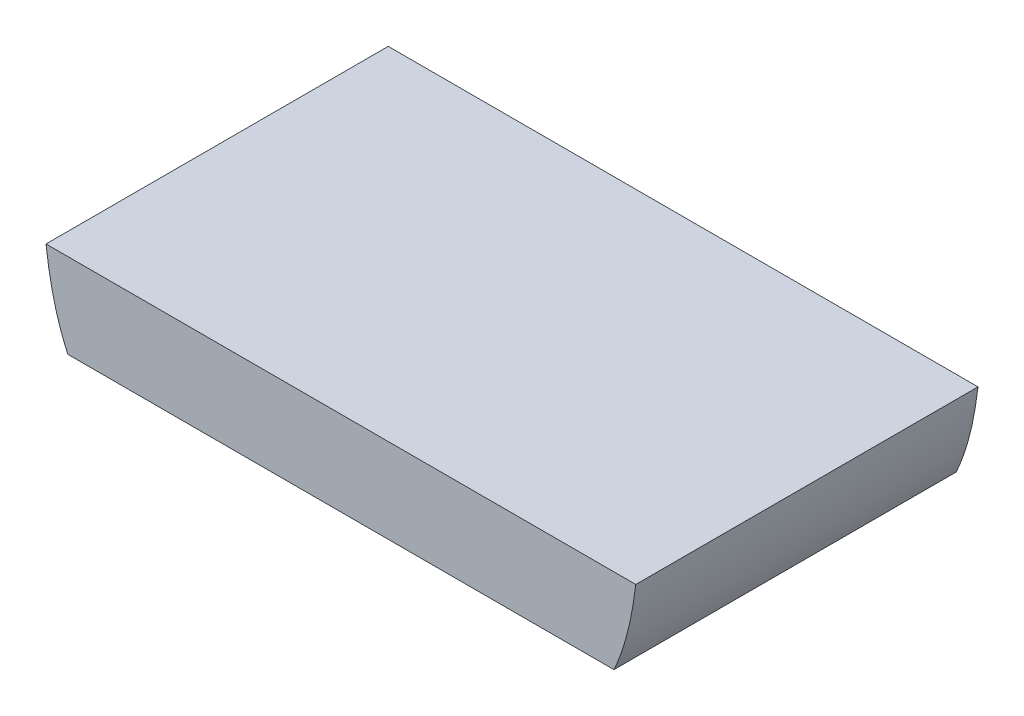
SolidWorks part; units mm, degrees
ref_plane "Front Plane" through (0, 0, 0) normal (0, 0, 1) x (1, 0, 0)
ref_plane "Top Plane" through (0, 0, 0) normal (0, 1, 0) x (1, 0, 0)
ref_plane "Right Plane" through (0, 0, 0) normal (1, 0, 0) x (0, 0, -1)
sketch "Sketch1" plane through (0, 0, 0) normal (0, 0, 1) x (1, 0, 0)
  line L0 (0, 0) -> (0, 222.758) construction
  line L2 (-350.1769, 222.758) -> (0, 222.758)
  line L3 (0, 222.758) -> (350.1769, 222.758)
  conic Q0 (350.1769, 222.758) -> (0, 0) control (323.6021, 0) rho 0.570465
  conic Q1 (-350.1769, 222.758) -> (0, 0) control (-323.6021, 0) rho 0.570465
extrude "Boss-Extrude1" add sketch "Sketch1" against normal blind 203.2 and the other way blind 203.2 contours Q0 Q1 L2 L3
sketch "Sketch6" plane through (0, 0, 0) normal (1, 0, 0) x (0, 0, -1)
  line L0 (0, 0) -> (402.7895, 12.7)
  line L1 (0, 0) -> (0, 317.8845) construction
  line L2 (0, 0) -> (-402.7895, 12.7)
  dimension "D1" = 12.7
ref_plane "Plane1" through (304.8, 0, 0) normal (1, 0, 0) x (0, 0, -1)
ref_plane "Plane2" [suppressed] through (0, 0, 401.32) normal (0, 0, 1) x (1, 0, 0)
sketch "Sketch29" plane through (0, 0, 0) normal (1, 0, 0) x (0, 0, -1)
  line L0 (0, 7.9367) -> (74.9675, 7.9367)
  line L1 (74.9675, 7.9367) -> (308.7791, 142.4931)
  line L3 (308.7791, 142.4931) -> (642.4614, 142.4931)
  point P6 (0, -63.5)
sweep "Engine Line" [suppressed] add path "Sketch29" circular profile diameter 12.7 parameters "D3"=12.7
sketch "Sketch42" plane through (0, 0, 0) normal (0, 0, 1) x (1, 0, 0)
  circle A0 centre (0, 6.35) radius 6.35
extrude "Boss-Extrude2" [suppressed] add sketch "Sketch42" against normal blind 635
sketch "Sketch43" plane through (0, 0, -203.2) normal (0, 0, -1) x (-1, 0, 0)
  circle A0 centre (0, 209.4482) radius 6.35
extrude "Boss-Extrude3" [suppressed] add sketch "Sketch43" along normal blind 142.748
ref_plane "Plane4" through (0, 0, 381) normal (0, 0, 1) x (1, 0, 0)
sketch "Sketch41" plane through (0, 0, 381) normal (0, 0, 1) x (1, 0, 0)
  line L0 (-0.3885, -71.0751) -> (-0.3885, 316.4102) construction
  conic Q0 (-0.3885, -71.0751) -> (301.9685, 246.7379) control (301.9685, -71.1416) rho 0.504796
  conic Q1 (-0.3885, -71.0751) -> (-302.7456, 246.7379) control (-302.7456, -71.1416) rho 0.504796
ref_plane "Plane5" through (350.1769, 0, 0) normal (1, 0, 0) x (0, 0, -1)
sketch "Sketch44" plane through (350.1769, 0, 0) normal (1, 0, 0) x (0, 0, -1)
  circle A0 centre (-360.0842, 200.1725) radius 12.7
sketch "Sketch45" plane through (0, 0, 0) normal (0, 0, 1) x (1, 0, 0)
  line L0 (-363.6888, 122.174) -> (403.1456, 122.174)
  line L1 (-350.1769, 222.758) -> (350.1769, 222.758) construction
  dimension "D1" = 100.584
split "Split1" trim tools "Sketch45" bodies to split 103 resulting bodies 127
